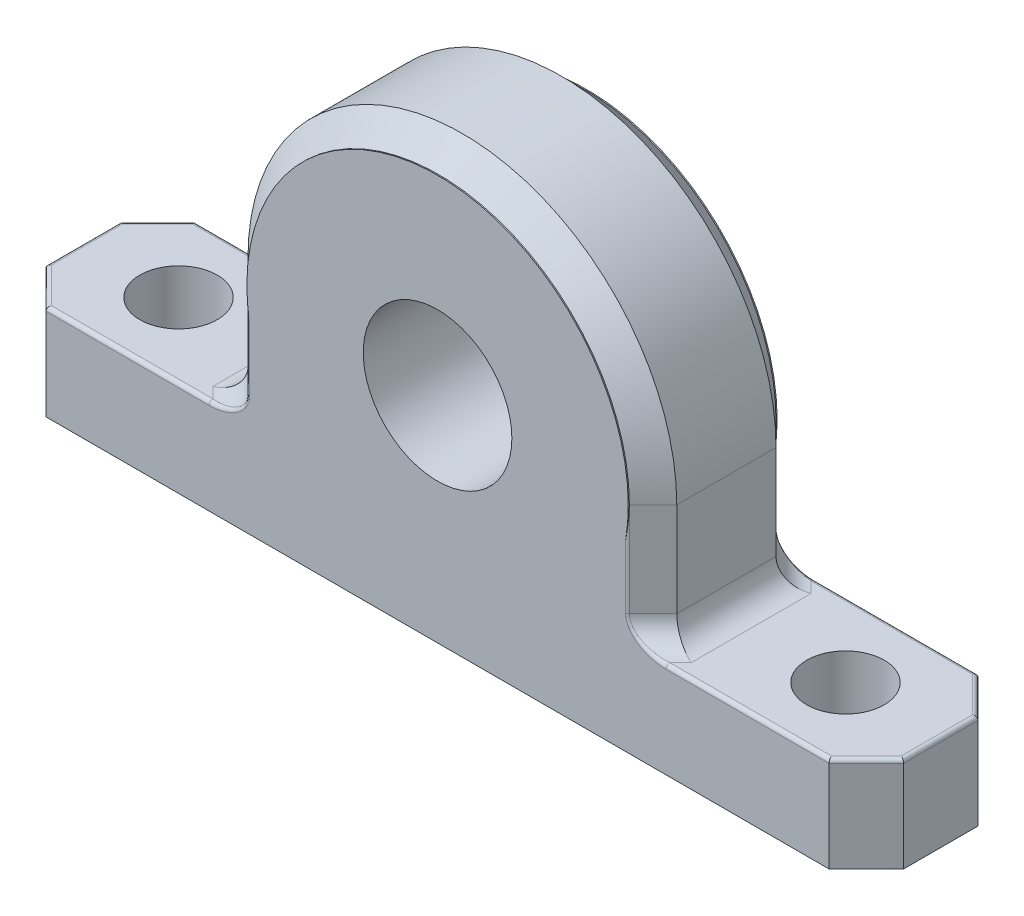
SolidWorks part; units mm, degrees
ref_plane "Front Plane" through (0, 0, 0) normal (0, 0, 1) x (1, 0, 0)
ref_plane "Top Plane" through (0, 0, 0) normal (0, 1, 0) x (1, 0, 0)
ref_plane "Right Plane" through (0, 0, 0) normal (1, 0, 0) x (0, 0, -1)
sketch "Sketch1" plane through (0, 0, 0) normal (0, 0, 1) x (1, 0, 0)
  line L0 (14.2875, 0) -> (14.2875, -7.9375)
  line L1 (14.2875, -7.9375) -> (28.575, -7.9375)
  line L2 (28.575, -7.9375) -> (28.575, -14.2875)
  line L3 (28.575, -14.2875) -> (-28.575, -14.2875)
  line L4 (-28.575, -14.2875) -> (-28.575, -7.9375)
  line L5 (-28.575, -7.9375) -> (-14.2875, -7.9375)
  line L6 (-14.2875, -7.9375) -> (-14.2875, 0)
  circle A0 centre (0, 0) radius 4.7625
  arc A1 (14.2875, 0) -> (-14.2875, 0) centre (0, 0) ccw
  circle A2 centre (0, 0) radius 10.7156
  point P12 (0, 10.7156)
  point P13 (0, 4.7625)
  dimension "shaft dia" = 9.525
  dimension "D1" = 21.4312
sketch "Sketch2" plane through (0, 0, 0) normal (0, 1, 0) x (1, 0, 0)
  line L0 (0, 4.9609) -> (0, -4.9609) construction
  line L1 (-22.225, 0) -> (22.225, 0) construction
  circle A0 centre (22.225, 0) radius 2.5797
  circle A1 centre (-22.225, 0) radius 2.5797
  dimension "Overall Width" = 9.9219
sketch "Sketch3" plane through (0, 0, 0) normal (0, 0, 1) x (1, 0, 0)
  line L0 (14.2875, 0) -> (14.2875, -7.9375) construction
  line L1 (28.575, -7.9375) -> (28.575, -14.2875) construction
  line L2 (14.2875, -7.9375) -> (28.575, -7.9375) construction
  line L3 (28.575, -14.2875) -> (-28.575, -14.2875) construction
  line L4 (-28.575, -14.2875) -> (-28.575, -7.9375) construction
  line L5 (-28.575, -7.9375) -> (-14.2875, -7.9375) construction
  line L6 (-14.2875, -7.9375) -> (-14.2875, 0) construction
  line L7 (14.2875, 0) -> (14.2875, -7.9375)
  line L8 (28.575, -7.9375) -> (28.575, -14.2875)
  line L9 (14.2875, -7.9375) -> (28.575, -7.9375)
  line L10 (28.575, -14.2875) -> (-28.575, -14.2875)
  line L11 (-28.575, -14.2875) -> (-28.575, -7.9375)
  line L12 (-28.575, -7.9375) -> (-14.2875, -7.9375)
  line L13 (-14.2875, -7.9375) -> (-14.2875, 0)
  arc A0 (14.2875, 0) -> (-14.2875, 0) centre (0, 0) ccw construction
  circle A1 centre (0, 0) radius 10.7156 construction
  arc A2 (14.2875, 0) -> (-14.2875, 0) centre (0, 0) ccw
  circle A3 centre (0, 0) radius 10.7156
extrude "Extrude1" add sketch "Sketch3" along normal up to vertex (4.9609 mm away) and the other way up to vertex (4.9609 mm away) up to point (0, 0, 4.9609) other way up to point (0, 0, -4.9609)
sketch "Sketch4" plane through (0, -7.9375, 0) normal (0, 1, 0) x (1, 0, 0)
  line L0 (-28.575, 4.9609) -> (-28.575, 2.4805)
  line L1 (-28.575, -4.9609) -> (-28.575, 4.9609) construction
  line L2 (-28.575, 2.4805) -> (-26.0945, 4.9609)
  line L3 (-14.2875, 4.9609) -> (-28.575, 4.9609) construction
  line L4 (-26.0945, 4.9609) -> (-28.575, 4.9609)
  line L5 (0, 0) -> (0, 4.9609) construction
  line L6 (0, 0) -> (-22.225, 0) construction
  line L7 (26.0945, 4.9609) -> (28.575, 4.9609)
  line L8 (28.575, 2.4805) -> (26.0945, 4.9609)
  line L9 (28.575, 4.9609) -> (28.575, 2.4805)
  line L10 (28.575, -4.9609) -> (28.575, -2.4805)
  line L11 (28.575, -2.4805) -> (26.0945, -4.9609)
  line L12 (26.0945, -4.9609) -> (28.575, -4.9609)
  line L13 (-26.0945, -4.9609) -> (-28.575, -4.9609)
  line L14 (-28.575, -2.4805) -> (-26.0945, -4.9609)
  line L15 (-28.575, -4.9609) -> (-28.575, -2.4805)
  circle A0 centre (-22.225, 0) radius 2.5797 construction
  circle A1 centre (22.225, 0) radius 2.5797 construction
  circle A2 centre (-22.225, 0) radius 2.5797
  circle A3 centre (22.225, 0) radius 2.5797
  dimension "D1" = 45
  dimension "D2" = 2.4805
extrude "Cut-Extrude1" cut sketch "Sketch4" against normal through all
chamfer "Chamfer3" distance 1.6536 angle 45 6 edges at (-14.2875, -3.9687, -4.9609) (0, 14.2875, -4.9609) (14.2875, -3.9687, -4.9609) (-14.2875, -3.9687, 4.9609) (0, 14.2875, 4.9609) (14.2875, -3.9687, 4.9609)
fillet "Fillet6" radius 1.6536 6 edges at (14.2875, -7.9375, 0) (13.4607, -7.9375, -4.1341) (13.4607, -7.9375, 4.1341) (-13.4607, -7.9375, -4.1341) (-13.4607, -7.9375, 4.1341) (-14.2875, -7.9375, 0)
fillet "Fillet7" radius 0.254 20 edges at (20.5335, -7.9375, -4.9609) (13.3188, -7.4532, -4.9609) (12.6339, -3.1419, -4.9609) (0, 12.6339, -4.9609) (-12.6339, -3.1419, -4.9609) (-13.3188, -7.4532, -4.9609) (20.5335, -7.9375, 4.9609) (13.3188, -7.4532, 4.9609) (12.6339, -3.1419, 4.9609) (0, 12.6339, 4.9609) (-12.6339, -3.1419, 4.9609) (-13.3188, -7.4532, 4.9609) (27.3348, -7.9375, 3.7207) (28.575, -7.9375, 0) (27.3348, -7.9375, -3.7207) (-20.5335, -7.9375, -4.9609) (-27.3348, -7.9375, -3.7207) (-28.575, -7.9375, 0) (-27.3348, -7.9375, 3.7207) (-20.5335, -7.9375, 4.9609)
chamfer "Chamfer4" distance 0.381 angle 45 2 edges at (10.7156, 0, -4.9609) (10.7156, 0, 4.9609)
sketch "Sketch5" plane through (0, 0, 0) normal (1, 0, 0) x (0, 0, -1)
  line L0 (-4.4529, 9.7234) -> (-3.4369, 9.7234)
  line L1 (0, 10.7156) -> (0, 4.7625) construction
  line L2 (4.4529, 10.7156) -> (4.4529, 9.7234)
  line L4 (4.4529, 9.7234) -> (3.4369, 9.7234)
  line L5 (-3.4369, 9.7234) -> (-3.4369, 8.5328)
  line L6 (-3.4369, 8.5328) -> (-4.8339, 8.5328)
  line L7 (-4.3259, 7.6121) -> (-4.3259, 7.7391)
  line L8 (-4.9609, 4.7625) -> (4.9609, 4.7625)
  line L9 (-4.3259, 7.6121) -> (-4.9609, 7.6121)
  line L10 (-4.4529, 10.7156) -> (4.4529, 10.7156)
  line L11 (3.4369, 9.7234) -> (3.4369, 8.5328)
  line L12 (-4.9609, 7.6121) -> (-4.9609, 4.7625)
  line L13 (-4.4529, 10.7156) -> (-4.4529, 9.7234)
  line L15 (-4.3259, 7.7391) -> (-4.8339, 7.7391)
  line L16 (-4.8339, 7.7391) -> (-4.8339, 8.5328)
  line L17 (0, 10.7156) -> (0, 14.2875) construction
  line L18 (0, 14.2875) -> (0, 0) construction
  line L19 (3.4369, 8.5328) -> (4.8339, 8.5328)
  line L20 (4.8339, 7.7391) -> (4.8339, 8.5328)
  line L21 (4.3259, 7.7391) -> (4.8339, 7.7391)
  line L22 (4.3259, 7.6121) -> (4.3259, 7.7391)
  line L23 (4.3259, 7.6121) -> (4.9609, 7.6121)
  line L24 (4.9609, 7.6121) -> (4.9609, 4.7625)
  line L27 (3.3073, 14.2875) -> (-3.3073, 14.2875) construction
  point P9 (0, 7.7391)
  dimension "D1" = 5.9531
  dimension "D2" = 0.9922
  dimension "D3" = 1.1906
  dimension "D6" = 1.016
  dimension "D5" = 0.635
  dimension "D7" = 0.127
  dimension "D8" = 0.127
  dimension "D9" = 0.508
revolve "Revolve1" add sketch "Sketch5" angle 360 about L0
chamfer "Chamfer5" distance 0.127 angle 45 12 edges at (-7.6121, 0, 4.9609) (-4.7625, 0, 4.9609) (-8.5328, 0, 4.8339) (-7.7391, 0, 4.8339) (-10.7156, 0, 4.4529) (-9.7234, 0, 4.4529) (-4.7625, 0, -4.9609) (-7.6121, 0, -4.9609) (-7.7391, 0, -4.8339) (-8.5328, 0, -4.8339) (-9.7234, 0, -4.4529) (-10.7156, 0, -4.4529)
fillet "Fillet8" radius 0.635 2 edges at (-8.5328, 0, 3.4369) (-8.5328, 0, -3.4369)
sketch "Sketch6" plane through (0, 0, 4.9609) normal (0, 0, 1) x (1, 0, 0)
  circle A0 centre (0, 0) radius 12.7082
extrude "Boss-Extrude1" add sketch "Sketch6" against normal up to surface (9.9219 mm away) up to face at (11.0966, 0, -4.9609)
sketch "Sketch7" plane through (0, 0, 4.9609) normal (0, 0, 1) x (1, 0, 0)
  circle A0 centre (0, 0) radius 4.953
  dimension "D1" = 9.906
extrude "Cut-Extrude2" cut sketch "Sketch7" against normal up to next
equation "\"D1@Sketch1\"=\"I@Sketch1\"*.75"
equation "\"D2@Sketch4\" = \"Overall Width@Sketch2\" / 4"
equation "\"D1@Chamfer3\" = \"Overall Width@Sketch2\" / 6"
equation "\"D1@Fillet6\"=\"D1@Chamfer3\""
equation "\"D2@Sketch5\"=\"D1@Sketch5\"/6"
equation "\"D3@Sketch5\"=\"D2@Sketch5\"*1.2"
